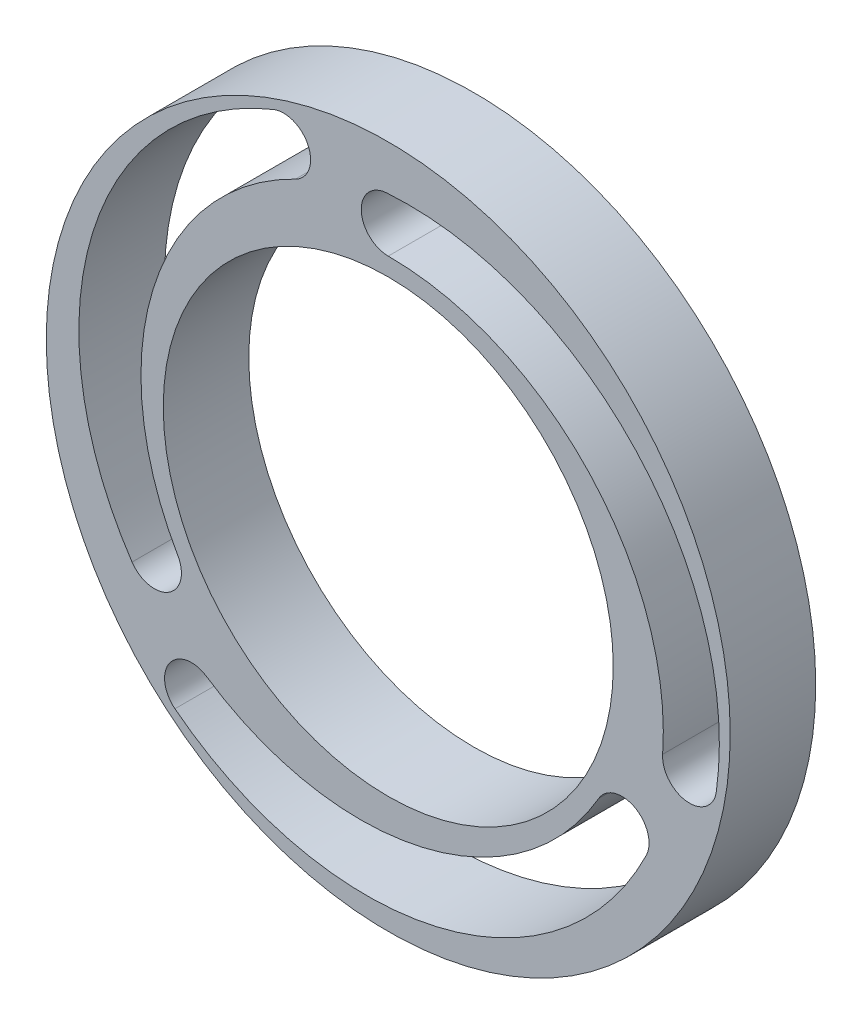
SolidWorks part; units mm, degrees
material "1060 Alloy"
ref_plane "Front Plane" through (0, 0, 0) normal (0, 0, 1) x (1, 0, 0)
ref_plane "Top Plane" through (0, 0, 0) normal (0, 1, 0) x (1, 0, 0)
ref_plane "Right Plane" through (0, 0, 0) normal (1, 0, 0) x (0, 0, -1)
sketch "Sketch2" plane through (0, 0, 0) normal (0, 0, 1) x (1, 0, 0)
  circle A0 centre (0, 0) radius 25
  circle A1 centre (0, 0) radius 38
  dimension "D1" = 50
  dimension "D2" = 76
sketch "Sketch1" plane through (0, 0, 0) normal (0, 0, 1) x (1, 0, 0)
  line L0 (0, 0) -> (0, 30) construction
  line L1 (0, 0) -> (33.4835, -5.904) construction
  line L2 (33.4835, -5.904) -> (37.4227, -6.5986) construction
  circle A0 centre (0, 0) radius 25
  circle A1 centre (0, 0) radius 38
  circle A2 centre (0, 30) radius 3
  circle A3 centre (33.4835, -5.904) radius 3
  arc A4 (-0.2083, 32.9928) -> (36.4544, -6.3204) centre (2.194, -1.519) cw
  arc A5 (30.4908, -5.695) -> (0, 27) centre (0, -3.5651) ccw
  dimension "D1" = 50
  dimension "D2" = 76
  dimension "D5" = 6
  dimension "D6" = 6
  dimension "D8" = 3
  dimension "D3" = 100
  dimension "D4" = 4
  dimension "D7" = 30
extrude "Boss-Extrude2" add sketch "Sketch2" along normal blind 9.5
extrude "Cut-Extrude1" cut sketch "Sketch1" along normal blind 9.5 contours A2 | A5 A3 A4 A2 | A3 region at (0, 30, 0) region at (22.7183, 17.6216, 0) region at (33.4835, -5.904, 0)
ref_axis "Axis1" through (0, 0, 9.5) along (0, 0, -1)
pattern_circular "CirPattern1" count 3 over 360 about axis through (0, 0, 9.5) along (0, 0, -1) of "Cut-Extrude1"
